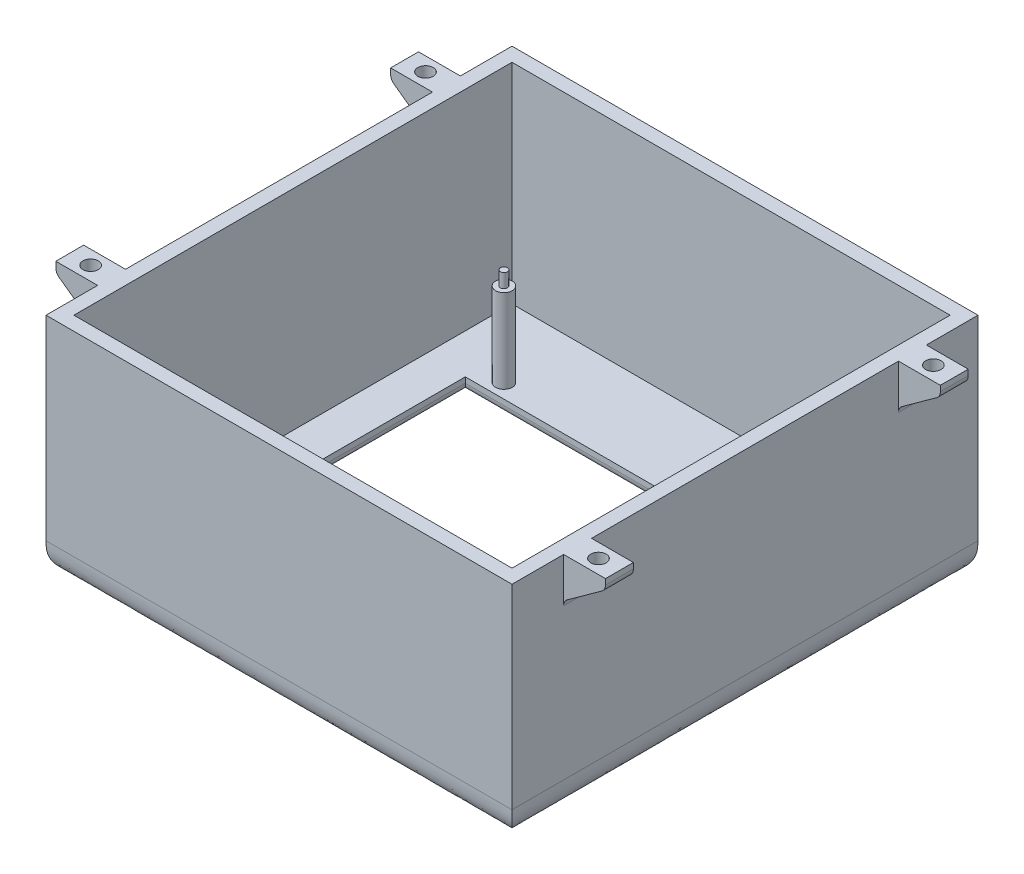
SolidWorks part; units mm, degrees
ref_plane "Ebene vorne" through (0, 0, 0) normal (0, 0, 1) x (1, 0, 0)
ref_plane "Ebene oben" through (0, 0, 0) normal (0, 1, 0) x (1, 0, 0)
ref_plane "Ebene rechts" through (0, 0, 0) normal (1, 0, 0) x (0, 0, -1)
sketch "Skizze1" plane through (0, 0, 0) normal (0, 1, 0) x (1, 0, 0)
  line L0 (-57.4441, 0) -> (108.4227, 0) construction
  line L1 (-83.5, 83.5) -> (83.5, 83.5)
  line L2 (-83.5, 83.5) -> (-83.5, -83.5)
  line L3 (-83.5, -83.5) -> (83.5, -83.5)
  line L4 (83.5, 83.5) -> (83.5, -83.5)
  line L5 (0, 55.397) -> (0, -92.4842) construction
  dimension "D1" = 167
  dimension "D2" = 167
extrude "Aufsatz-Linear austragen1" add sketch "Skizze1" along normal blind 80
sketch "Skizze2" plane through (0, 80, 0) normal (0, 1, 0) x (1, 0, 0)
  line L0 (0, 52.0751) -> (0, -71.1014) construction
  line L1 (-78.5, 78.5) -> (78.5, 78.5)
  line L2 (-78.5, 78.5) -> (-78.5, -78.5)
  line L3 (-78.5, -78.5) -> (78.5, -78.5)
  line L4 (78.5, 78.5) -> (78.5, -78.5)
  line L5 (-41.5118, 0) -> (56.2139, 0) construction
  line L6 (-83.5, 83.5) -> (-83.5, -83.5) construction
  line L7 (83.5, 83.5) -> (-83.5, 83.5) construction
  dimension "D1" = 5
  dimension "D2" = 5
extrude "Schnitt-Linear austragen1" cut sketch "Skizze2" against normal blind 75
sketch "Platine" plane through (0, 5, 0) normal (0, 1, 0) x (1, 0, 0)
  line L0 (0, 25.5089) -> (0, -13.445) construction
  line L1 (-17.8492, 0) -> (15.1436, 0) construction
  line L2 (33.515, 54.5281) -> (33.515, -95.4394) construction
  line L3 (58.415, 73.5618) -> (58.415, -76.4057) construction
  line L6 (24.1073, 11.505) -> (87.4465, 11.505) construction
  line L7 (33.8429, -13.445) -> (97.1821, -13.445) construction
  line L8 (-58.415, 56.095) -> (33.515, 56.095)
  line L9 (33.515, 56.095) -> (58.415, 11.505)
  line L10 (58.415, 11.505) -> (58.415, -13.445)
  line L11 (58.415, -13.445) -> (33.515, -56.095)
  line L12 (33.515, -56.095) -> (-58.415, -56.095)
  line L13 (-58.415, -56.095) -> (-58.415, 56.095)
  dimension "D1" = 112.19
  dimension "D2" = 91.93
  dimension "D3" = 24.9
  dimension "D4" = 44.59
  dimension "D5" = 24.95
sketch "Skizze4" plane through (0, 5, 0) normal (0, 1, 0) x (1, 0, 0)
  line L1 (-58.415, -56.095) -> (-58.415, 56.095) construction
  line L2 (-58.415, 56.095) -> (33.515, 56.095) construction
  line L3 (33.515, -56.095) -> (-58.415, -56.095) construction
  line L4 (58.415, 11.505) -> (58.415, -13.445) construction
  circle A0 centre (-55.5494, 52.655) radius 2.985
  circle A1 centre (-55.5494, -53.3587) radius 3
  circle A2 centre (41.2513, -32.9612) radius 3
  circle A3 centre (41.2513, 36.7522) radius 3
  dimension "D9" = 5.97
  dimension "D10" = 6
  dimension "D11" = 6
  dimension "D12" = 6
  dimension "D1" = 2.8656
  dimension "D2" = 3.44
  dimension "D3" = 2.8656
  dimension "D4" = 2.7363
  dimension "D5" = 19.3428
  dimension "D6" = 17.1638
  dimension "D7" = 23.1337
  dimension "D8" = 17.1638
extrude "Aufsatz-Linear austragen2" add sketch "Skizze4" along normal blind 30
sketch "Skizze5" plane through (0, 35, 0) normal (0, 1, 0) x (1, 0, 0)
  circle A0 centre (-55.5494, 52.655) radius 1.25
  circle A1 centre (41.2513, 36.7522) radius 1.25
  circle A2 centre (41.2513, -32.9612) radius 1.25
  circle A3 centre (-55.5494, -53.3587) radius 1.25
  dimension "D1" = 2.5
  dimension "D2" = 2.5
  dimension "D3" = 2.5
  dimension "D4" = 2.5
extrude "Aufsatz-Linear austragen3" add sketch "Skizze5" along normal blind 5
sketch "Skizze6" plane through (0, 0, 0) normal (0, -1, 0) x (1, 0, 0)
  line L0 (29.767, 24.5) -> (29.767, 47.5)
  line L1 (-64.233, 47.5) -> (29.767, 47.5)
  line L2 (-64.233, 47.5) -> (-64.233, -47.5)
  line L3 (-64.233, -47.5) -> (29.767, -47.5)
  line L5 (0, 0) -> (0, 41.5649) construction
  line L6 (0, 0) -> (-36.8563, 0) construction
  line L7 (29.767, 24.5) -> (58.415, 24.5)
  line L8 (58.415, -73.5618) -> (58.415, 76.4057) construction
  line L9 (58.415, 24.5) -> (58.415, -24.5)
  line L10 (58.415, -24.5) -> (29.767, -24.5)
  line L12 (29.767, -24.5) -> (29.767, -47.5)
  point P4 (0, 0)
  dimension "D1" = 95
  dimension "D2" = 94
  dimension "D3" = 23
  dimension "D4" = 94
extrude "Schnitt-Linear austragen2" cut sketch "Skizze6" against normal blind 5
sketch "Skizze10" plane through (0, 80, 0) normal (0, 1, 0) x (1, 0, 0)
  line L0 (0, 0) -> (-140.2518, 0) construction
  line L1 (-140.2518, 0) -> (174.1265, 0) construction
  line L2 (0, 0) -> (0, -99.0125) construction
  line L3 (0, -99.0125) -> (0, 90.3805) construction
  line L4 (-83.5, 83.5) -> (-83.5, -83.5) construction
  line L5 (-83.5, 65) -> (-98.5, 65)
  line L6 (-83.5, 65) -> (-83.5, 55)
  line L7 (-83.5, 55) -> (-98.5, 55)
  line L8 (-98.5, 65) -> (-98.5, 55)
  line L9 (-83.5, -55) -> (-98.5, -55)
  line L10 (-98.5, -65) -> (-98.5, -55)
  line L11 (-83.5, -65) -> (-98.5, -65)
  line L12 (-83.5, -65) -> (-83.5, -55)
  line L13 (83.5, -65) -> (83.5, -55)
  line L14 (83.5, -65) -> (98.5, -65)
  line L15 (98.5, -65) -> (98.5, -55)
  line L16 (83.5, -55) -> (98.5, -55)
  line L17 (98.5, 65) -> (98.5, 55)
  line L18 (83.5, 55) -> (98.5, 55)
  line L19 (83.5, 65) -> (83.5, 55)
  line L20 (83.5, 65) -> (98.5, 65)
  line L21 (91, 65) -> (91, 55) construction
  line L22 (98.5, 60) -> (83.5, 60) construction
  circle A0 centre (91, 60) radius 2.75
  circle A1 centre (91, -60) radius 2.75
  circle A2 centre (-91, -60) radius 2.75
  circle A3 centre (-91, 60) radius 2.75
  dimension "D3" = 5.5
  dimension "D1" = 15
  dimension "D2" = 10
  dimension "D4" = 60
extrude "Aufsatz-Linear austragen4" add sketch "Skizze10" against normal blind 20
sketch "Skizze11" plane through (0, 0, -83.5) normal (0, 0, -1) x (-1, 0, 0)
  line L3 (0, 0) -> (0, 80) construction
  line L4 (-83.5, 80) -> (83.5, 80) construction
  line L7 (83.5, 65.6081) -> (98.5, 76.4455)
  line L8 (98.5, 60) -> (98.5, 80) construction
  line L9 (83.5, 80) -> (83.5, 0) construction
  line L10 (83.5, 65.6081) -> (83.5, 60)
  line L11 (83.5, 60) -> (98.5, 60)
  line L12 (98.5, 60) -> (98.5, 76.4455)
  line L13 (-98.5, 60) -> (-98.5, 76.4455)
  line L14 (-83.5, 60) -> (-98.5, 60)
  line L15 (-83.5, 65.6081) -> (-83.5, 60)
  line L16 (-83.5, 65.6081) -> (-98.5, 76.4455)
extrude "Schnitt-Linear austragen9" cut sketch "Skizze11" against normal through all
ref_plane "Ebene1" through (0, 74, 0) normal (0, 1, 0) x (1, 0, 0)
sketch "Skizze13" plane through (0, 74, 0) normal (0, 1, 0) x (1, 0, 0)
  line L0 (0, 0) -> (0, 94.861) construction
  line L1 (0, 94.861) -> (0, -99.5436) construction
  line L2 (96.6502, 0) -> (-112.8768, 0) construction
  circle A0 centre (91, 60) radius 4.5
  circle A1 centre (91, -60) radius 4.5
  circle A2 centre (-91, -60) radius 4.5
  circle A3 centre (-91, 60) radius 4.5
  dimension "D1" = 9
extrude "Schnitt-Linear austragen10" cut sketch "Skizze13" against normal blind 8
fillet "Verrundung3" radius 3 8 edges at (83.5, 65.6081, 60) (83.5, 65.6081, -60) (-83.5, 65.6081, 60) (-83.5, 65.6081, -60) (-98.5, 76.4455, -60) (-98.5, 76.4455, 60) (98.5, 76.4455, -60) (98.5, 76.4455, 60)
fillet "Verrundung4" radius 10 4 edges at (-83.5, 0, 0) (0, 0, -83.5) (0, 0, 83.5) (83.5, 0, 0) curvature continuous yes
fillet "Verrundung5" radius 3 8 edges at (29.767, 0, 36) (44.091, 0, 24.5) (58.415, 0, 0) (44.091, 0, -24.5) (29.767, 0, -36) (-17.233, 0, -47.5) (-64.233, 0, 0) (-17.233, 0, 47.5)
fillet "Verrundung6" radius 3 4 edges at (30.6457, 0.8787, -25.3787) (30.6457, 0.8787, 25.3787) (29.767, 4, -24.5) (29.767, 4, 24.5)
